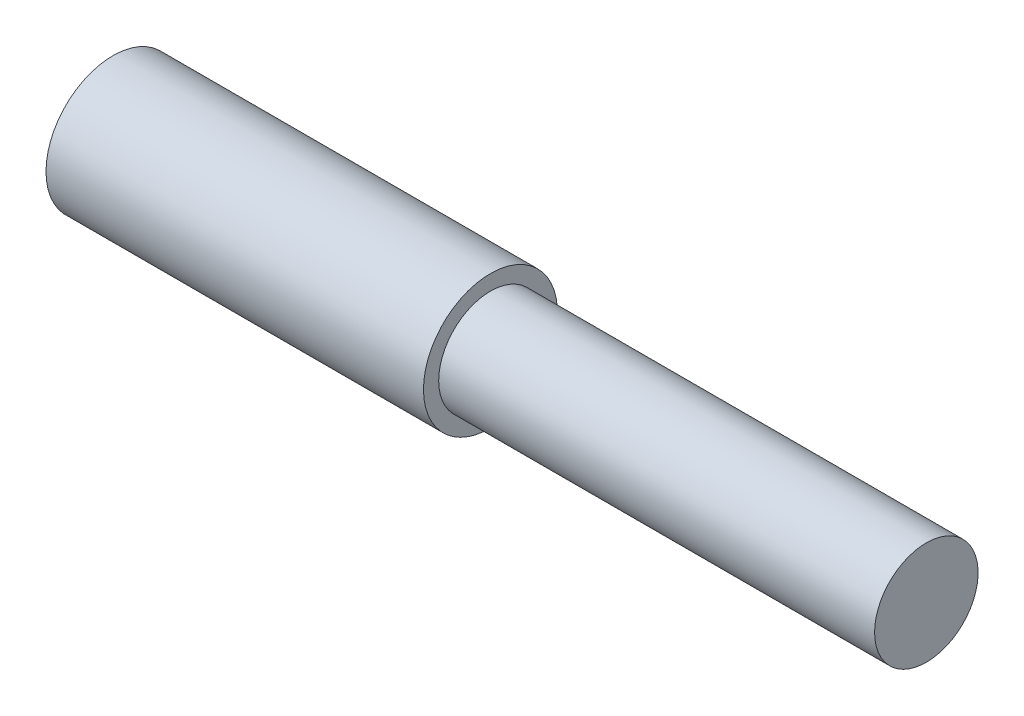
SolidWorks part; units mm, degrees
ref_plane "Front Plane" through (0, 0, 0) normal (0, 0, 1) x (1, 0, 0)
ref_plane "Top Plane" through (0, 0, 0) normal (0, 1, 0) x (1, 0, 0)
ref_plane "Right Plane" through (0, 0, 0) normal (1, 0, 0) x (0, 0, -1)
sketch "Sketch1" plane through (0, 0, 0) normal (0, 0, 1) x (1, 0, 0)
  line L0 (-9.4589, 0) -> (1.0894, 0) construction
  line L1 (0, 2.75) -> (-15.5, 2.75)
  line L2 (-15.5, 2.75) -> (-15.5, 0)
  line L3 (-15.5, 0) -> (17.9, 0)
  line L4 (0, 2.75) -> (0, 2.125)
  line L5 (0, 2.125) -> (0, 0) construction
  line L6 (0, 2.125) -> (17.9, 2.125)
  line L7 (17.9, 2.125) -> (17.9, 0)
  line L8 (5.5, 0) -> (5.5, 2.125) construction
  dimension "D1" = 5.5
  dimension "OD" = 5.5
  dimension "ID" = 4.25
  dimension "D2" = 12.4
  dimension "D3" = 15.5
revolve "Revolve1" add sketch "Sketch1" angle 360 about L0
ref_axis "Axis1" through (0, 0, 0) along (-1, 0, 0)
chamfer "Chamfer1" [suppressed] distance 1 angle 45
sketch "Sketch2" [suppressed] plane through (-5.5, 0, 0) normal (-1, 0, 0) x (0, 0, 1)
  circle A0 centre (0, 0) radius 4.75
  circle A1 centre (0, 0) radius 2.75 construction
  circle A2 centre (0, 0) radius 5.75
  dimension "D1" = 2
  dimension "D2" = 1
extrude "Boss-Extrude1" [suppressed] add sketch "Sketch2" against normal blind 30 separate body
sketch "Sketch3" [suppressed] plane through (0, 0, 0) normal (0, 0, 1) x (1, 0, 0)
  line L0 (-5.5, 2.75) -> (-5.5, -2.75) construction
  line L1 (-5.5, -0.8) -> (-4.7, -0.8)
  line L2 (-5.5, -0.8) -> (-5.5, 0.8)
  line L3 (-5.5, 0.8) -> (-4.7, 0.8)
  line L4 (-4.7, -0.8) -> (-4.7, 0.8)
  point P4 (-4.7, 0)
  dimension "D1" = 0.8
  dimension "D2" = 1.6
extrude "Boss-Extrude2" [suppressed] add sketch "Sketch3" along normal up to surface and the other way up to surface
pattern_circular "CirPattern1" [suppressed] count 4 over 360 reverse direction yes of bodies 103
pattern_linear "LPattern1" [suppressed] count 3 spacing 14.8 along (1, 0, 0) of bodies 104
